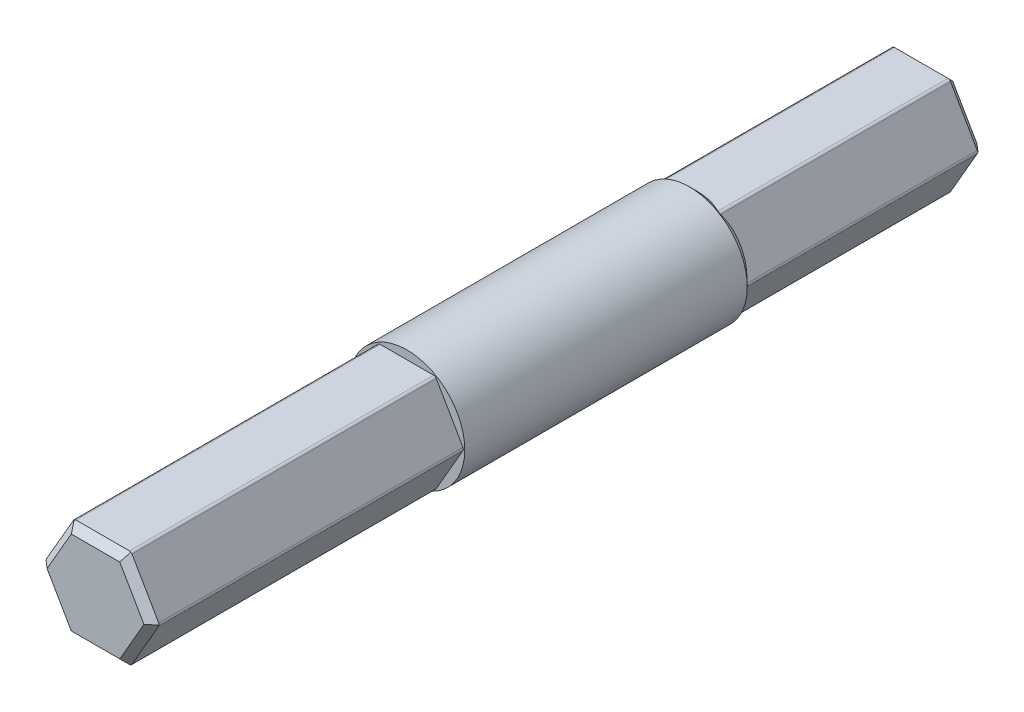
SolidWorks part; units mm, degrees
material "PETG"
ref_plane "Front Plane" through (0, 0, 0) normal (0, 0, 1) x (1, 0, 0)
ref_plane "Top Plane" through (0, 0, 0) normal (0, 1, 0) x (1, 0, 0)
ref_plane "Right Plane" through (0, 0, 0) normal (1, 0, 0) x (0, 0, -1)
sketch "Sketch1" plane through (0, 0, 0) normal (0, 0, 1) x (1, 0, 0)
  circle A0 centre (0, 0) radius 3.99
  dimension "Shaft Dia" = 7.98
extrude "Boss-Extrude1" add sketch "Sketch1" along normal blind 20
sketch "Sketch2" plane through (0, 0, 20) normal (0, 0, 1) x (1, 0, 0)
  line L1 (4, 0) -> (2, 3.4641) construction
  line L2 (2, 3.4641) -> (-2, 3.4641) construction
  line L3 (-2, 3.4641) -> (-4, 0) construction
  line L4 (-4, 0) -> (-2, -3.4641) construction
  line L5 (-2, -3.4641) -> (2, -3.4641) construction
  line L6 (2, -3.4641) -> (4, 0) construction
  line L7 (3.9221, 0) -> (1.961, 3.3966)
  line L8 (1.961, 3.3966) -> (-1.961, 3.3966)
  line L9 (-1.961, 3.3966) -> (-3.9221, 0)
  line L10 (-3.9221, 0) -> (-1.961, -3.3966)
  line L11 (-1.961, -3.3966) -> (1.961, -3.3966)
  line L12 (1.961, -3.3966) -> (3.9221, 0)
  circle A0 centre (0, 0) radius 3.4641 construction
  circle A1 centre (0, 0) radius 3.3966 construction
  dimension "Hex Circumscribed Nominal Dia" = 8
  dimension "Hex Flat To Flat Offset" = 0.0675
extrude "Boss-Extrude2" add sketch "Sketch2" along normal blind 21.5
sketch "Sketch3" plane through (0, 0, 0) normal (0, 0, -1) x (-1, 0, 0)
  line L0 (-1.961, 3.3966) -> (1.961, 3.3966) construction
  line L13 (3.9221, 0) -> (1.961, 3.3966)
  line L14 (1.961, 3.3966) -> (-1.961, 3.3966)
  line L15 (-1.961, 3.3966) -> (-3.9221, 0)
  line L16 (-3.9221, 0) -> (-1.961, -3.3966)
  line L17 (-1.961, -3.3966) -> (1.961, -3.3966)
  line L18 (1.961, -3.3966) -> (3.9221, 0)
  circle A1 centre (0, 0) radius 3.3966 construction
extrude "Boss-Extrude3" add sketch "Sketch3" along normal blind 16
chamfer "Chamfer1" distance 0.5 angle 45 12 edges at (0, -3.3966, 41.5) (-2.9415, -1.6983, 41.5) (-2.9415, 1.6983, 41.5) (0, 3.3966, 41.5) (2.9415, 1.6983, 41.5) (2.9415, -1.6983, 41.5) (0, -3.3966, -16) (2.9415, -1.6983, -16) (2.9415, 1.6983, -16) (0, 3.3966, -16) (-2.9415, 1.6983, -16) (-2.9415, -1.6983, -16)
fillet "Fillet1" radius 0.2 12 edges at (-1.961, 3.3966, -7.75) (-3.9221, 0, -7.75) (1.961, 3.3966, -7.75) (3.9221, 0, -7.75) (1.961, -3.3966, -7.75) (-1.961, -3.3966, -7.75) (1.961, -3.3966, 30.5) (-1.961, -3.3966, 30.5) (-3.9221, 0, 30.5) (-1.961, 3.3966, 30.5) (3.9221, 0, 30.5) (1.961, 3.3966, 30.5)
chamfer "Chamfer2" distance 0.5 angle 45 1 edges at (3.99, 0, 0)
equation "\"tol_dia_id_intfc\" = 0.0200mm ' For hole diameters - Interference fit"
equation "\"tol_dia_id_slip\"  = 0.0300mm ' For hole diameters - Slip fit"
equation "\"tol_dia_id_clear\" = 0.0500mm ' For hole diameters - Clearance fit"
equation "\"tol_dia_od_intfc\" = 0.0200mm ' For shaft diameters - Interference fit"
equation "\"tol_dia_od_slip\"  = 0.0300mm ' For shaft diameters - Slip fit"
equation "\"tol_dia_od_clear\" = 0.0500mm ' For shaft diameters - Clearance fit"
equation "\"tol_general_intfc\"= 0.0030mm ' For general parts (Horiz) - Interference fit"
equation "\"tol_general_slip\" = 0.0050mm ' For general parts (Horiz) - Slip fit"
equation "\"tol_general_clear\"= 0.0100mm ' For general parts (Horiz) - Clearance fit"
equation "\"tol_layer_intfc\"  = 0.0030mm ' For all parts (Vert) - Interference fit"
equation "\"tol_layer_slip\"   = 0.0050mm ' For all parts (Vert) - Slip fit"
equation "\"tol_layer_clear\"  = 0.0100mm ' For all parts (Vert) - Clearance fit"
equation "\"tol_corner_rad\"   = 0.100mm ' For corners that fit into other parts"
equation "\"Shaft Dia@Sketch1\" = \"nominal_dia\" - \"tol_dia_od_intfc\""
equation "\"nominal_dia\"= 8.00mm"
equation "\"Hex Circumscribed Nominal Dia@Sketch2\" = \"nominal_dia\""
equation "\"Hex Flat To Flat Offset@Sketch2\"=\"tol_general_slip\"+0.06250"
equation "\"D1@Fillet1\"=\"tol_corner_rad\"*2"
equation "\"D1@Boss-Extrude2\"=21.5"
